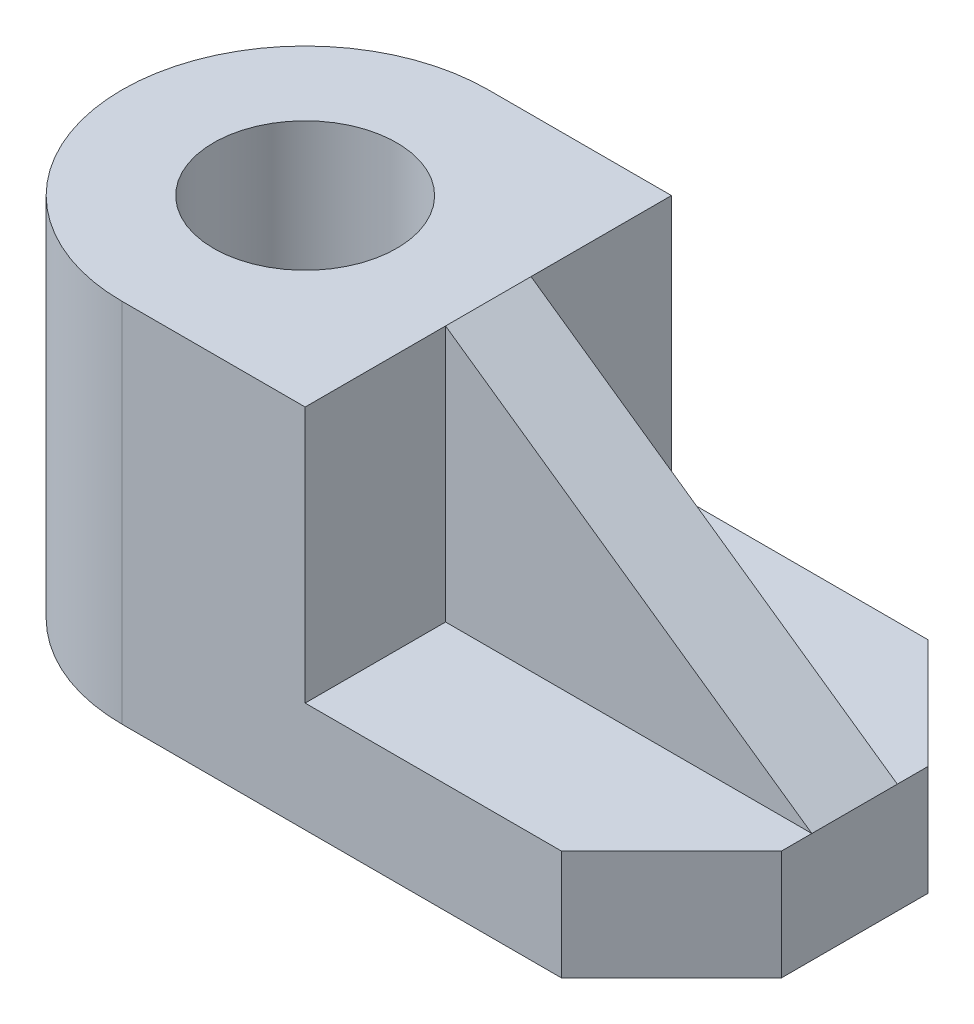
SolidWorks part; units mm, degrees
ref_plane "Front Plane" through (0, 0, 0) normal (0, 0, 1) x (1, 0, 0)
ref_plane "Top Plane" through (0, 0, 0) normal (0, 1, 0) x (1, 0, 0)
ref_plane "Right Plane" through (0, 0, 0) normal (1, 0, 0) x (0, 0, -1)
sketch "Sketch1" plane through (0, 0, 0) normal (0, 0, 1) x (1, 0, 0)
  line L0 (0, 0) -> (0, 762)
  line L1 (0, 762) -> (762, 762)
  line L2 (762, 762) -> (1524, 228.6)
  line L3 (1524, 228.6) -> (1524, 0)
  line L4 (1524, 0) -> (0, 0)
  dimension "D1" = 762
  dimension "D2" = 762
  dimension "D3" = 1524
  dimension "D4" = 228.6
extrude "Boss-Extrude2" add sketch "Sketch1" along normal blind 381 and the other way blind 381
fillet "Fillet1" radius 381 2 edges at (0, 381, -381) (0, 381, 381)
sketch "Sketch2" plane through (0, 762, 0) normal (0, 1, 0) x (1, 0, 0)
  line L0 (1524, 381) -> (1524, -381) construction
  line L1 (762, 381) -> (1524, 381)
  line L2 (762, 381) -> (762, 88.9)
  line L3 (762, 88.9) -> (1524, 88.9)
  line L4 (1524, 381) -> (1524, 88.9)
  line L5 (1524, 0) -> (0, 0) construction
  line L6 (1524, -381) -> (1524, -88.9)
  line L7 (762, -88.9) -> (1524, -88.9)
  line L8 (762, -381) -> (762, -88.9)
  line L9 (762, -381) -> (1524, -381)
  dimension "D1" = 292.1
extrude "Cut-Extrude1" cut sketch "Sketch2" against normal up to vertex (533.4 mm away) up to point (1524, 228.6, -381)
sketch "Sketch4" plane through (0, 762, 0) normal (0, 1, 0) x (1, 0, 0)
  circle A0 centre (381, 0) radius 190.5
  dimension "D1" = 381
extrude "Cut-Extrude2" cut sketch "Sketch4" against normal through all
chamfer "Chamfer1" distance 228.6 angle 45 2 edges at (1524, 114.3, 381) (1524, 114.3, -381)
